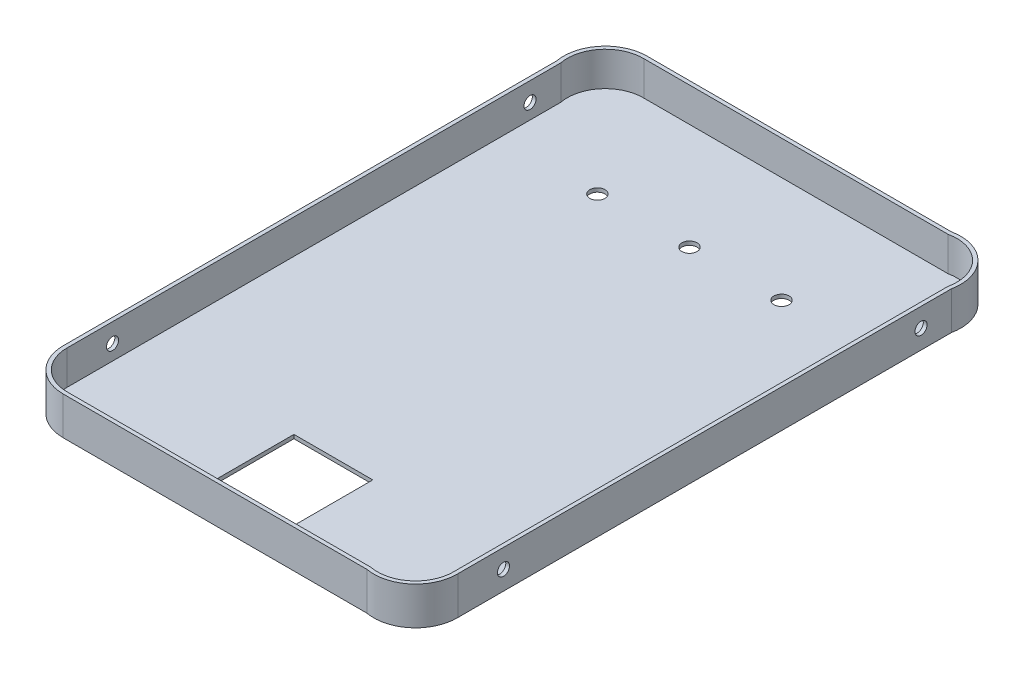
SolidWorks part; units mm, degrees
ref_plane "前视基准面" through (0, 0, 0) normal (0, 0, 1) x (1, 0, 0)
ref_plane "上视基准面" through (0, 0, 0) normal (0, 1, 0) x (1, 0, 0)
ref_plane "右视基准面" through (0, 0, 0) normal (1, 0, 0) x (0, 0, -1)
other "Configuration Table"
sketch "草圖1" plane through (0, 0, 0) normal (0, 1, 0) x (1, 0, 0)
  line L0 (-41.2381, 59.1667) -> (-41.2381, -70.8333)
  line L9 (-30.2381, -81.8333) -> (49.7619, -81.8333)
  line L10 (62.7619, 59.1667) -> (62.7619, -70.8333)
  line L11 (-30.2381, 72.1667) -> (49.7619, 72.1667)
  arc A4 (-41.2381, -70.8333) -> (-30.2381, -81.8333) centre (-30.2381, -70.8333) ccw
  arc A5 (49.7619, -81.8333) -> (62.7619, -70.8333) centre (51.7634, -71.017) ccw
  arc A6 (49.7619, 72.1667) -> (62.7619, 59.1667) centre (51.9899, 61.3947) cw
  arc A7 (-30.2381, 72.1667) -> (-41.2381, 59.1667) centre (-30.4217, 61.1682) ccw
  dimension "D1" = 104
  dimension "D2" = 154
extrude "填料-伸長1" add sketch "草圖1" along normal blind 10
shell "薄殼5" thickness 1 removed face at (10.3562, 10, 5.2391)
sketch "草圖2" plane through (-41.2381, 0, 0) normal (-1, 0, 0) x (0, 0, 1)
  line L2 (-59.1667, 10) -> (70.8333, 10) construction
  line L3 (-59.1667, 0) -> (70.8333, 0) construction
  line L4 (3.8333, 26.8821) -> (3.8333, -26.8821)
  circle A0 centre (-51.1667, 5) radius 1.6
  circle A1 centre (58.8333, 5) radius 1.6
  point P5 (3.8333, 0)
  point P7 (3.8333, 0)
  dimension "D1" = 55
  dimension "D2" = 5
  dimension "D3" = 130
extrude "除料-伸長1" cut sketch "草圖2" against normal through all and the other way through all contours A0 | A1
sketch "草圖6" plane through (0, 0, 0) normal (0, -1, 0) x (-1, 0, 0)
  line L0 (41.2381, 59.1667) -> (41.2381, -70.8333) construction
  line L1 (-0.3756, -72.0119) -> (-21.1482, -72.0119)
  line L2 (-0.3756, -72.0119) -> (-0.3756, -51.6548)
  line L3 (-0.3756, -51.6548) -> (-21.1482, -51.6548)
  line L4 (-21.1482, -72.0119) -> (-21.1482, -51.6548)
  line L5 (-0.3756, -72.0119) -> (-21.1482, -51.6548) construction
  line L6 (-0.3756, -51.6548) -> (-21.1482, -72.0119) construction
  line L7 (30.2381, -81.8333) -> (-49.7619, -81.8333) construction
  point P0 (-10.7619, -61.8333)
  dimension "D1" = 52
  dimension "D2" = 20
extrude "除料-伸長2" cut sketch "草圖6" against normal through all contours L2 L3 L4 L1
sketch "草圖9" plane through (0, 0, 0) normal (0, -1, 0) x (1, 0, 0)
  line L0 (49.7619, -72.1667) -> (-30.2381, -72.1667) construction
  line L2 (9.7619, -43.164) -> (9.7619, -72.1667)
  circle A0 centre (-14.4881, -43.164) radius 2
  circle A2 centre (34.0119, -43.164) radius 2
  circle A3 centre (9.7619, -43.164) radius 2
  point P2 (9.7619, -72.1667)
  point P5 (9.7619, -43.164)
  dimension "D2" = 4
  dimension "D3" = 2
  dimension "D1" = 48.5
extrude "除料-伸長3" cut sketch "草圖9" against normal up to next contours A2 | A3 | A0
